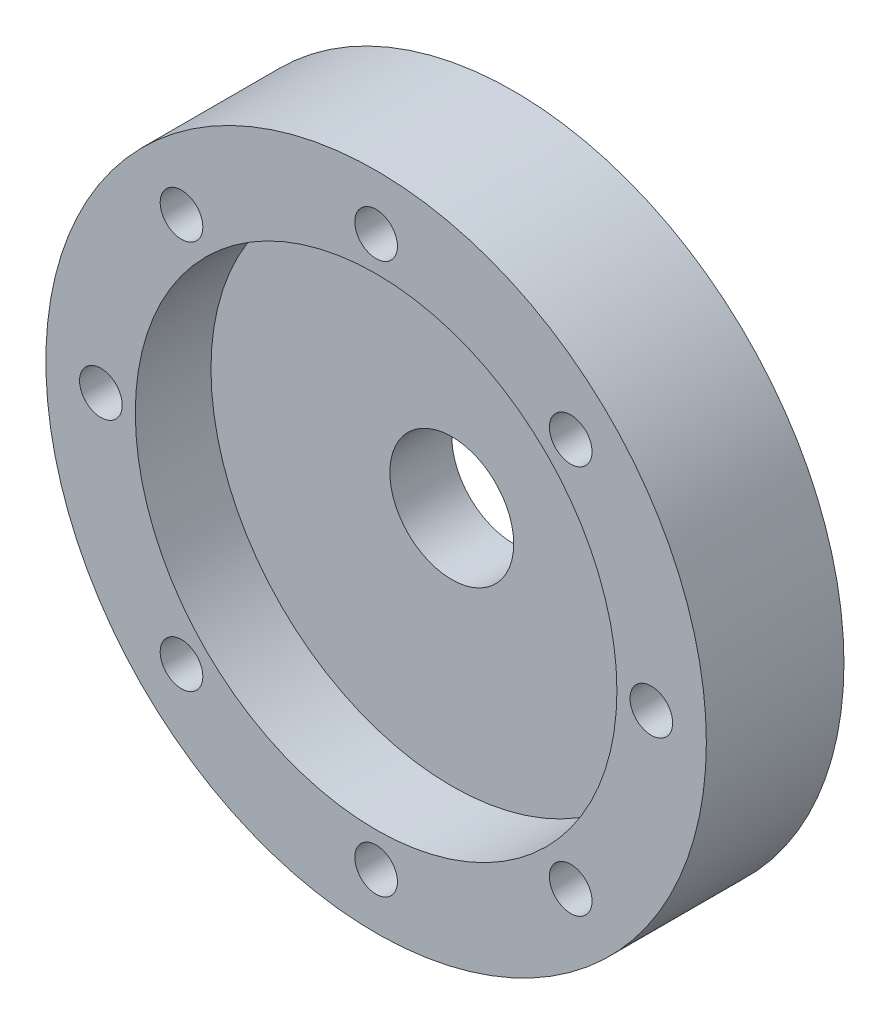
SolidWorks part; units mm, degrees
ref_plane "Front Plane" through (0, 0, 0) normal (0, 0, 1) x (1, 0, 0)
ref_plane "Top Plane" through (0, 0, 0) normal (0, 1, 0) x (1, 0, 0)
ref_plane "Right Plane" through (0, 0, 0) normal (1, 0, 0) x (0, 0, -1)
ref_axis "Axis1" through (0, 0, 5.5) along (0, 0, -1)
sketch "Sketch6" plane through (0, 0, 0) normal (0, 0, 1) x (1, 0, 0)
  line L0 (0, 0) -> (0, 20) construction
  circle A0 centre (0, 0) radius 24
  circle A1 centre (0, 20) radius 1.55
  circle A2 centre (14.1421, 14.1421) radius 1.55
  circle A3 centre (20, 0) radius 1.55
  circle A4 centre (14.1421, -14.1421) radius 1.55
  circle A5 centre (0, -20) radius 1.55
  circle A6 centre (-14.1421, -14.1421) radius 1.55
  circle A7 centre (-20, 0) radius 1.55
  circle A8 centre (-14.1421, 14.1421) radius 1.55
  circle A9 centre (0, 0) radius 4.5
  point P21 (0, 0)
  dimension "D1" = 8
extrude "Boss-Extrude1" add sketch "Sketch6" along normal blind 10
sketch "Sketch8" plane through (0, 0, 0) normal (0, 0, -1) x (-1, 0, 0)
  line L0 (0, 20) -> (0, 0) construction
  circle A0 centre (0, 20) radius 3.5
  circle A1 centre (14.1421, 14.1421) radius 3.5
  circle A2 centre (20, 0) radius 3.5
  circle A3 centre (14.1421, -14.1421) radius 3.5
  circle A4 centre (0, -20) radius 3.5
  circle A5 centre (-14.1421, -14.1421) radius 3.5
  circle A6 centre (-20, 0) radius 3.5
  circle A7 centre (-14.1421, 14.1421) radius 3.5
  point P20 (0, 0)
  dimension "D1" = 8
extrude "Cut-Extrude6" cut sketch "Sketch8" against normal blind 4
sketch "Sketch9" plane through (0, 0, 10) normal (0, 0, 1) x (1, 0, 0)
  circle A0 centre (0, 0) radius 17.5
extrude "Cut-Extrude7" cut sketch "Sketch9" against normal blind 5.5
